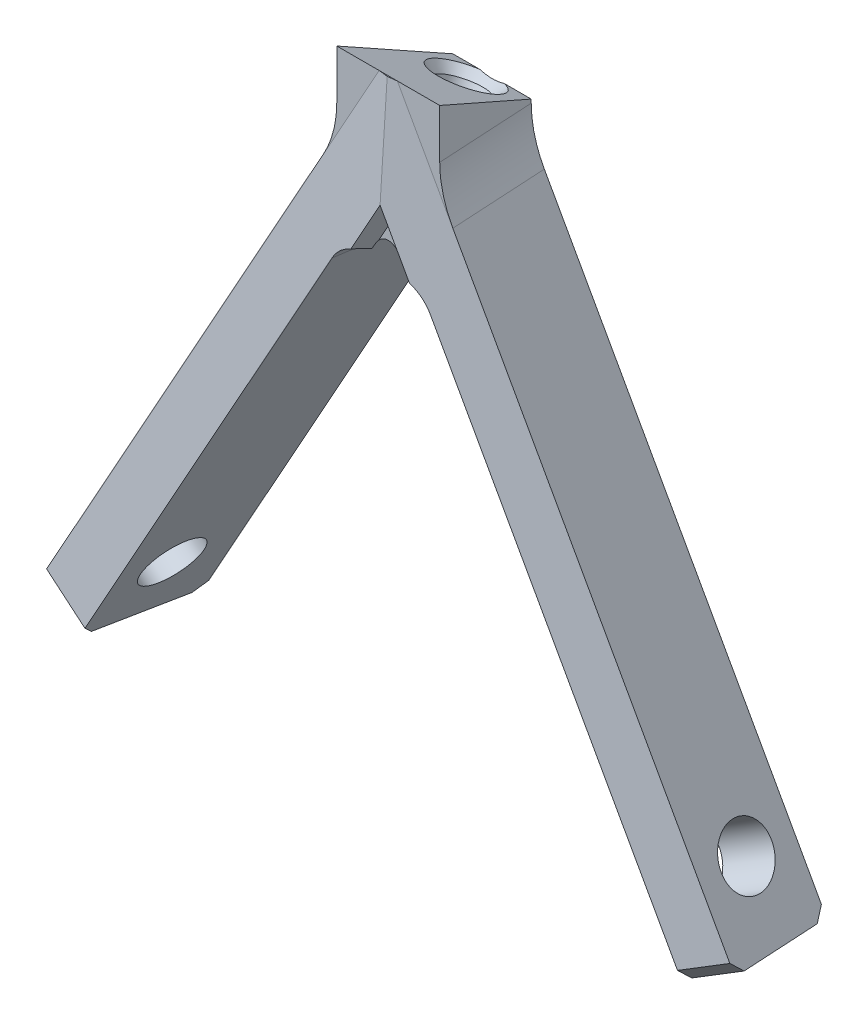
SolidWorks part; units mm, degrees
ref_plane "Top" through (0, 0, 0) normal (0, 0, 1) x (1, 0, 0)
ref_plane "Front" through (0, 0, 0) normal (0, 1, 0) x (1, 0, 0)
ref_plane "Right" through (0, 0, 0) normal (1, 0, 0) x (0, 0, -1)
sketch "Sketch5" plane through (0, 0, 0) normal (0, 0, 1) x (1, 0, 0)
  line L0 (0, 0) -> (-24.9091, -44.7895)
  line L1 (0, 0) -> (24.9091, -44.7895)
  line L2 (0, 0) -> (0, -56.2591)
  dimension "D1" = 58.16
  dimension "D2" = 51.25
  dimension "D3" = 51.25
sketch "Sketch6" plane through (0, 0, 0) normal (1, 0, 0) x (0, 0, -1)
  line L0 (0, 0) -> (-11.5702, -41.5699) construction
  line L1 (0, 0) -> (0, -44.7902) construction
  line L2 (0, 0) -> (0, -56.2591) construction
  line L3 (0, -44.7902) -> (-11.5702, -41.5699) construction
  line L4 (0, 0) -> (11.5702, -3.2203) construction
  line L5 (11.5702, -3.2203) -> (0, -44.7902) construction
  dimension "D1" = 43.15
  dimension "D2" = 12.01
ref_plane "Plane6" through (0, 0, 0) normal (0.8661, 0.4816, -0.1341) x (-0.1172, -0.0652, -0.991)
ref_plane "Plane7" through (0, 0, 0) normal (0.8816, -0.4547, 0.1266) x (0, -0.2681, -0.9634)
sketch "Sketch7" plane through (0, 0, 0) normal (0.8661, 0.4816, -0.1341) x (-0.1172, -0.0652, -0.991)
  line L1 (-5, -58) -> (5, -58)
  line L2 (5, -58) -> (5, 0)
  line L4 (5, 0) -> (-5, 0)
  line L5 (-5, 0) -> (-5, -58)
  line L6 (0, 0) -> (0, -51.25) construction
  dimension "D1" = 10
  dimension "D2" = 5
  dimension "D3" = 58
extrude "Boss-Extrude4" add sketch "Sketch7" along normal blind 5
hole_wizard "M5 Clearance Hole1" positions "Sketch19" profile "Sketch20" hole size "M5" standard "DIN" end condition through all
sketch "Sketch19" plane through (0, 0, 0) normal (-0.8661, -0.4816, 0.1341) x (0.1172, 0.0652, 0.991)
  point P0 (0, -51.25)
sketch "Sketch20" plane through (24.9091, -44.7895, 0) normal (-0.273, 0.6802, 0.6802) x (0.4188, -0.5525, 0.7206)
  line L0 (0, 0) -> (0, 30.7423)
  line L1 (0, 30.7423) -> (2.75, 30.7423)
  line L2 (2.75, 30.7423) -> (2.75, 0)
  line L5 (2.75, 0) -> (0, 0)
  line L11 (0, -6.35) -> (0, 107.95) construction
  dimension "Thru Hole Dia." = 5.5
  dimension "Thru Hole Depth" = 30.7423
mirror "Mirror7" about plane through (0, 0, 0) normal (1, 0, 0) of "M5 Clearance Hole1", "Boss-Extrude4"
sketch "Sketch21" plane through (0, 0, 0) normal (0, 1, 0) x (1, 0, 0)
  line L0 (-3.7445, 5.6252) -> (3.7445, 5.6252)
  line L1 (3.7445, 5.6252) -> (4.9161, -4.2846)
  line L2 (4.9161, -4.2846) -> (-4.9161, -4.2846)
  line L3 (-4.9161, -4.2846) -> (-3.7445, 5.6252)
extrude "Boss-Extrude6" add sketch "Sketch21" against normal blind 5 and the other way blind 5
sketch "Sketch22" plane through (0, 0, -0.258) normal (1, 0, 0) x (0, 0, -1)
  line L0 (5.3672, 5) -> (-4.5425, 10.0123)
  line L1 (-4.5425, 10.0123) -> (-4.5425, 5)
  line L3 (-4.5425, 5) -> (5.3672, 5) construction
  line L4 (-4.5425, 5) -> (5.3672, 5)
  line L5 (-4.5425, 5) -> (-4.5425, 2.734) construction
  dimension "D1" = 26.83
extrude "Boss-Extrude9" add sketch "Sketch22" along normal up to surface and the other way up to surface up to face at (4.3303, 3.7041, -0.6703) other way up to face at (-4.3303, 3.7041, -0.6703)
hole_wizard "Ø4.4 (4.4) Diameter Hole1" positions "Sketch23" profile "Sketch24" hole size "Ø4.4" standard "DIN" end condition through all
sketch "Sketch23" plane through (0, 6.247, -3.1597) normal (0, 0.8923, -0.4513) x (1, 0, 0)
  point P0 (0, 0)
sketch "Sketch24" plane through (0, 6.247, -3.1597) normal (1, 0, 0) x (0, 0.4513, 0.8923)
  line L0 (0, 0) -> (0, 54.7597)
  line L1 (0, 54.7597) -> (2.2, 54.7597)
  line L2 (2.2, 54.7597) -> (2.2, 0)
  line L5 (2.2, 0) -> (0, 0)
  line L11 (0, -6.35) -> (0, 107.95) construction
  dimension "Thru Hole Dia." = 4.4
  dimension "Thru Hole Depth" = 54.7597
fillet "Fillet1" radius 10 2 edges at (4.3303, 2.4082, -0.6703) (-4.3303, 2.4082, -0.6703)
sketch "Sketch25" plane through (28.1898, -50.6886, 0) normal (0.486, -0.8739, 0) x (0.8739, 0.486, 0)
  line L0 (4.2846, -5.6252) -> (-0.6703, -4.9549)
  line L1 (4.2846, -5.6252) -> (-0.761, -5.6252)
  line L2 (-0.761, -5.6252) -> (-0.6703, -4.9549)
  line L3 (0.5796, 4.2846) -> (-0.6703, -4.9549) construction
extrude "Boss-Extrude10" add sketch "Sketch25" against normal up to vertex (58 mm away) up to point (3.7445, 2.0824, -5.6251)
sketch "Sketch26" plane through (-28.1898, -50.6886, 0) normal (-0.486, -0.8739, 0) x (0.8739, -0.486, 0)
  line L0 (-4.2846, -5.6252) -> (0.761, -5.6252)
  line L1 (0.761, -5.6252) -> (0.6703, -4.9549)
  line L2 (0.6703, -4.9549) -> (-4.2846, -5.6252)
  line L3 (-0.6703, 4.9549) -> (0.6703, -4.9549) construction
extrude "Boss-Extrude11" add sketch "Sketch26" against normal up to vertex (58 mm away) up to point (-3.7445, 2.0824, -5.6251)
sketch "Sketch27" plane through (0, 0, 0) normal (-0.486, 0.8739, 0) x (0.8739, 0.486, 0)
  line L0 (0.6703, -4.9549) -> (0.5796, -4.2846)
  line L1 (0.5796, -4.2846) -> (5.6252, -4.2846)
  line L2 (5.6252, -4.2846) -> (0.6703, -4.9549)
extrude "Boss-Extrude12" add sketch "Sketch27" along normal up to surface (10.1147 mm away) up to plane "Right"
sketch "Sketch28" plane through (0, 0, 0) normal (0.486, 0.8739, 0) x (0.8739, -0.486, 0)
  line L0 (-0.6703, -4.9549) -> (-5.6252, -4.2846)
  line L1 (-5.6252, -4.2846) -> (-0.5796, -4.2846)
  line L2 (-0.5796, -4.2846) -> (-0.6703, -4.9549)
extrude "Boss-Extrude13" add sketch "Sketch28" along normal up to surface (1.0422 mm away) up to plane "Right"
sketch "Sketch29" plane through (0, 0, 4.2846) normal (0, 0, -1) x (-1, 0, 0)
  line L0 (4.9161, 10.0123) -> (4.9161, 5.3126) construction
  line L1 (-4.9161, 10.0123) -> (4.9161, 10.0123)
  line L2 (-4.9161, 10.0123) -> (-4.9161, 13.5978)
  line L3 (-4.9161, 13.5978) -> (4.9161, 13.5978)
  line L4 (4.9161, 10.0123) -> (4.9161, 13.5978)
extrude "Cut-Extrude2" cut sketch "Sketch29" against normal blind 4.915
chamfer "Chamfer2" distance 1.5 angle 45 2 edges at (1.7219, -1.9037, 4.2846) (-1.7219, -1.9037, 4.2846) first distance on face at (26.2456, -47.1929, 0) first distance on face at (-23.5725, -42.3862, 0)
fillet "Fillet2" radius 4 2 edges at (2.7288, -5, -0.3351) (-2.7288, -5, -0.3351)
chamfer "Chamfer5" distance 1 angle 45 4 edges at (29.7295, -49.8323, -5.6252) (-29.7295, -49.8323, -5.6252) (-30.9407, -49.1587, 4.6197) (30.9407, -49.1587, 4.6197)
chamfer "Chamfer6" distance 0.8 angle 45 1 edges at (0, 7.24, -1.1965)
